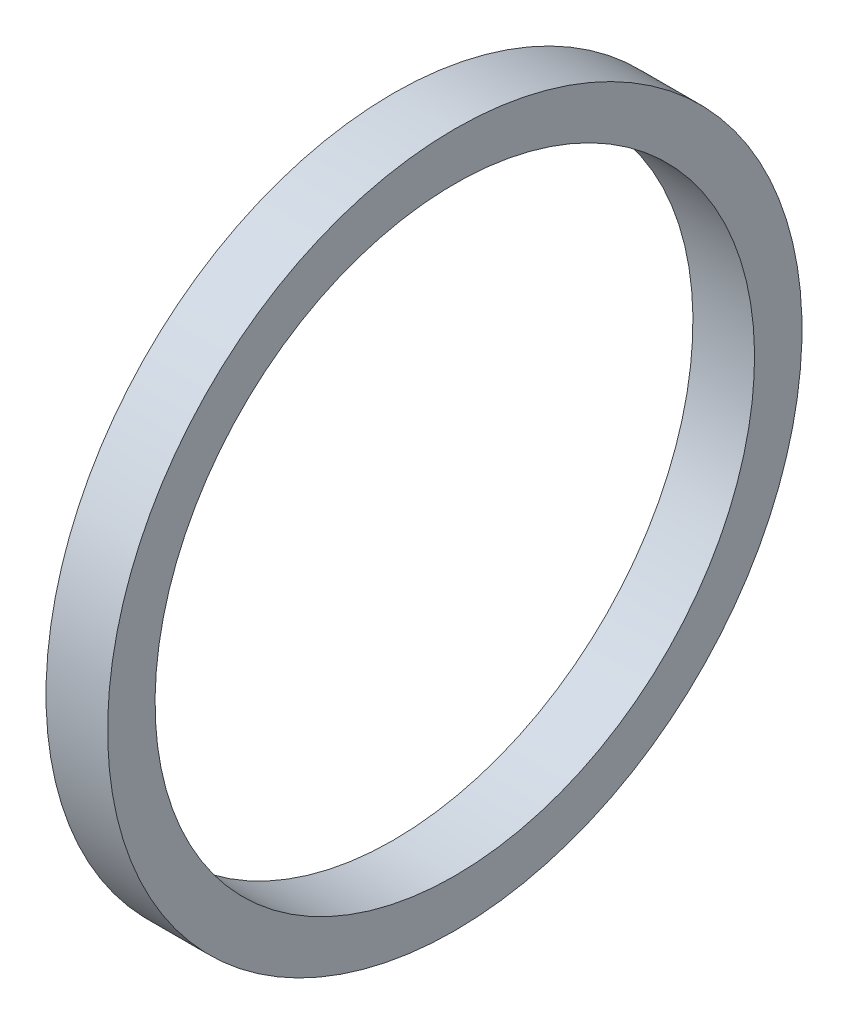
SolidWorks part; units mm, degrees
material "6061-T6 (SS)"
ref_plane "Front Plane" through (0, 0, 0) normal (0, 0, 1) x (1, 0, 0)
ref_plane "Top Plane" through (0, 0, 0) normal (0, 1, 0) x (1, 0, 0)
ref_plane "Right Plane" through (0, 0, 0) normal (1, 0, 0) x (0, 0, -1)
sketch "Sketch1" plane through (-24.9481, 0, 0) normal (-1, 0, 0) x (0, 0, 1)
  circle A0 centre (0, 0) radius 13.9746 construction
  circle A1 centre (0, 0) radius 13.9746
  circle A2 centre (0, 0) radius 12.065
  dimension "D1" = 24.13
extrude "Boss-Extrude1" add sketch "Sketch1" along normal up to surface (2.48 mm away)
